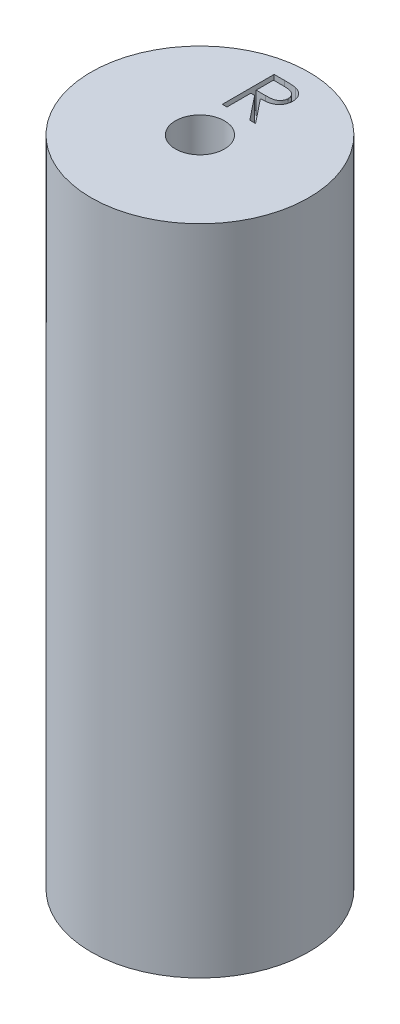
SolidWorks part; units mm, degrees
ref_plane "Front Plane" through (0, 0, 0) normal (0, 0, 1) x (1, 0, 0)
ref_plane "Top Plane" through (0, 0, 0) normal (0, 1, 0) x (1, 0, 0)
ref_plane "Right Plane" through (0, 0, 0) normal (1, 0, 0) x (0, 0, -1)
sketch "Sketch1" plane through (0, 0, 0) normal (0, 1, 0) x (1, 0, 0)
  circle A0 centre (0, 0) radius 10
  dimension "D1" = 20
extrude "Boss-Extrude1" add sketch "Sketch1" along normal blind 4
sketch "Sketch2" plane through (0, 4, 0) normal (0, 1, 0) x (1, 0, 0)
  circle A1 centre (0, 0) radius 3.5
  circle A2 centre (0, 0) radius 8
  circle A3 centre (0, 0) radius 8
  circle A4 centre (0, 0) radius 10 construction
  circle A5 centre (0, 0) radius 10
  circle M2 centre (0, 0) radius 10
  dimension "D2" = 7
  dimension "D1" = 2
extrude "Boss-Extrude2" add sketch "Sketch2" along normal blind 52 contours A1 | A3 M2 region at (0, 4, 0) region at (-9.7172, 4, 0)
sketch "Sketch3" plane through (0, 56, 0) normal (0, 1, 0) x (1, 0, 0)
  circle A0 centre (0, 0) radius 10 construction
  circle A1 centre (0, 0) radius 10
extrude "Boss-Extrude3" add sketch "Sketch3" along normal blind 4
sketch "Sketch4" plane through (0, 60, 0) normal (0, 1, 0) x (1, 0, 0)
  line L0 (-9.3832, 3.4577) -> (9.3832, 3.4577) construction
  circle A0 centre (0, 0) radius 10 construction
  text T0 "R" font "Century Gothic" height in points 18
extrude "Cut-Extrude1" cut sketch "Sketch4" against normal blind 2
sketch "Sketch5" plane through (0, 60, 0) normal (0, 1, 0) x (1, 0, 0)
  circle A0 centre (0, 0) radius 2.25
  dimension "D1" = 4.5
extrude "Cut-Extrude2" cut sketch "Sketch5" against normal blind 50
